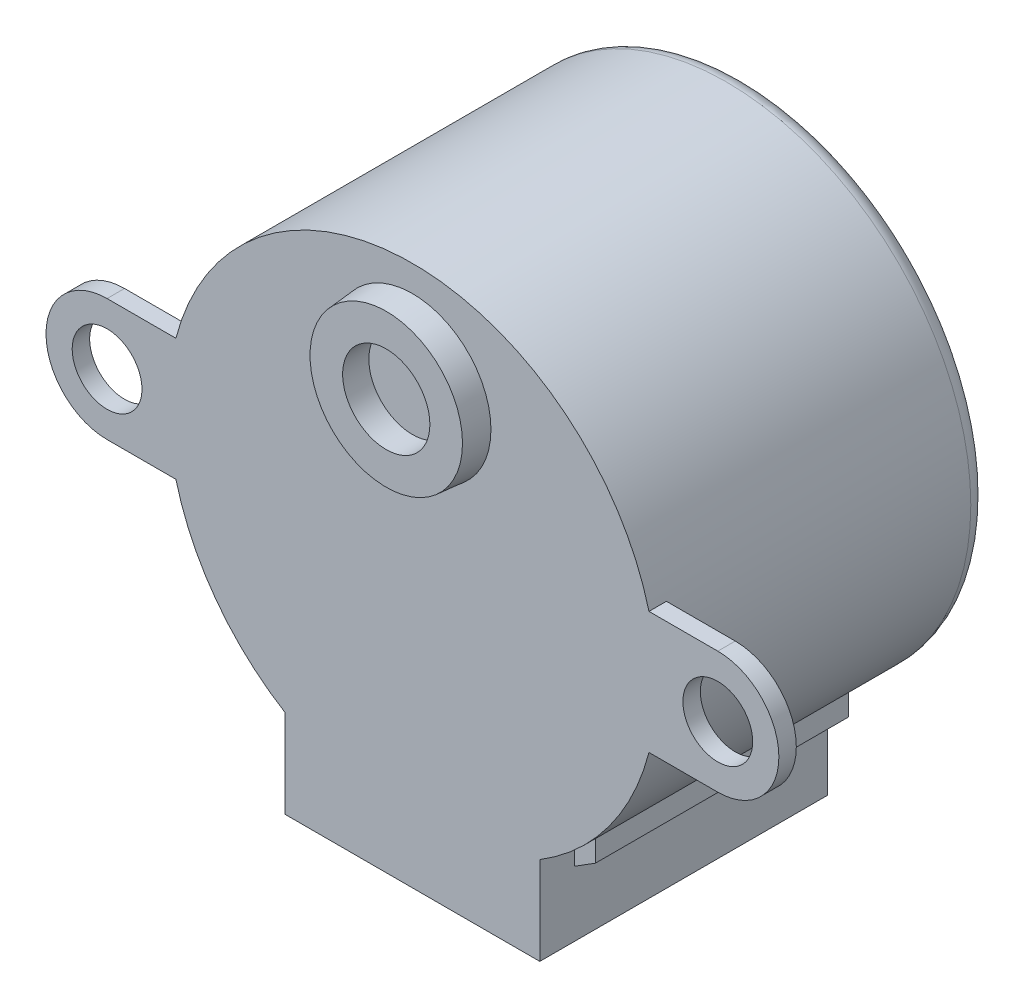
SolidWorks part; units mm, degrees
ref_plane "Front Plane" through (0, 0, 0) normal (0, 0, 1) x (1, 0, 0)
ref_plane "Top Plane" through (0, 0, 0) normal (0, 1, 0) x (1, 0, 0)
ref_plane "Right Plane" through (0, 0, 0) normal (1, 0, 0) x (0, 0, -1)
sketch "Sketch1" plane through (0, 0, 0) normal (0, 0, 1) x (1, 0, 0)
  circle A0 centre (0, 0) radius 14
  dimension "D1" = 28
extrude "Boss-Extrude3" add sketch "Sketch1" along normal blind 19
sketch "Sketch5" plane through (0, 0, 19) normal (0, 0, 1) x (1, 0, 0)
  line L0 (0, 0) -> (0, -22.9361) construction
  line L1 (-7.3, -11.9461) -> (-7.3, -17)
  line L2 (-7.3, -17) -> (7.3, -17)
  line L3 (7.3, -11.9461) -> (7.3, -17)
  circle A0 centre (0, 0) radius 14 construction
  arc A1 (7.3, -11.9461) -> (-7.3, -11.9461) centre (0, 0) cw
  point P9 (0, -17)
  dimension "D1" = 14.6
  dimension "D2" = 17
extrude "Boss-Extrude5" add sketch "Sketch5" against normal blind 16.5
sketch "Sketch6" plane through (0, 0, 2.5) normal (0, 0, -1) x (-1, 0, 0)
  line L0 (-8.4859, -11.135) -> (-8.4859, -12.5311)
  line L1 (-8.4859, -12.5311) -> (-7.3, -13.2752)
  line L2 (-7.3, -17) -> (-7.3, -11.9461) construction
  line L3 (-7.3, -13.2752) -> (-7.3, -11.9461)
  line L4 (-7.3, -11.9461) -> (-8.4859, -11.135)
  line L5 (0, 10.45) -> (0, -10.45) construction
  line L6 (7.3, -13.2752) -> (7.3, -11.9461)
  line L7 (8.4859, -12.5311) -> (7.3, -13.2752)
  line L8 (8.4859, -11.135) -> (8.4859, -12.5311)
  line L9 (7.3, -11.9461) -> (8.4859, -11.135)
  circle A0 centre (0, 0) radius 14 construction
  arc A1 (-7.3, -11.9461) -> (7.3, -11.9461) centre (0, 0) ccw construction
extrude "Boss-Extrude7" add sketch "Sketch6" against normal blind 14.5
fillet "Fillet1" radius 1 1 edges at (14, 0, 0)
sketch "Sketch7" plane through (0, 0, 19) normal (0, 0, 1) x (1, 0, 0)
  line L0 (0, 0) -> (20.6615, 0) construction
  line L1 (13.5554, 3.5) -> (17.5, 3.5)
  line L2 (17.5, -3.5) -> (13.5554, -3.5)
  circle A0 centre (17.5, 0) radius 2
  arc A1 (7.3, -11.9461) -> (-7.3, -11.9461) centre (0, 0) ccw construction
  arc A2 (17.5, 3.5) -> (17.5, -3.5) centre (17.5, 0) cw
  arc A3 (13.5554, 3.5) -> (13.5554, -3.5) centre (0, 0) cw
  dimension "D1" = 4
  dimension "D2" = 17.5
  dimension "D3" = 7
extrude "Boss-Extrude8" add sketch "Sketch7" against normal blind 1
mirror "Mirror1" about plane through (0, 0, 0) normal (1, 0, 0) of "Boss-Extrude8"
sketch "Sketch8" plane through (0, 0, 19) normal (0, 0, 1) x (1, 0, 0)
  line L0 (0, 0) -> (0, 16) construction
  circle A0 centre (0, 8) radius 4.5
  point P5 (0, 0)
  point P6 (0, 0)
  dimension "D1" = 9
  dimension "D2" = 8
extrude "Boss-Extrude9" add sketch "Sketch8" along normal blind 1.5 draft 5
sketch "Sketch9" plane through (0, 0, 20.5) normal (0, 0, 1) x (1, 0, 0)
  circle A0 centre (0, 8) radius 2.5
  dimension "D1" = 5
extrude "Cut-Extrude1" cut sketch "Sketch9" against normal up to surface (1.5 mm away) up to face at (4.5, 8, 19)
sketch "Sketch10" plane through (0, 0, 0) normal (0, 0, -1) x (-1, 0, 0)
  line L0 (-1.4331, 5.31) -> (-0.684, 8.7977)
  line L1 (-0.684, 8.7977) -> (0.684, 8.7977)
  line L2 (0, 11.275) -> (0, -11.275) construction
  line L3 (1.4331, 5.31) -> (0.684, 8.7977)
  line L4 (2.7414, 4.7681) -> (5.7373, 6.7046)
  line L5 (4.7681, 2.7414) -> (6.7046, 5.7373)
  line L6 (5.7373, 6.7046) -> (6.7046, 5.7373)
  line L7 (5.31, 1.4331) -> (8.7977, 0.684)
  line L8 (5.31, -1.4331) -> (8.7977, -0.684)
  line L9 (8.7977, 0.684) -> (8.7977, -0.684)
  line L10 (4.7681, -2.7414) -> (6.7046, -5.7373)
  line L11 (2.7414, -4.7681) -> (5.7373, -6.7046)
  line L12 (6.7046, -5.7373) -> (5.7373, -6.7046)
  line L13 (1.4331, -5.31) -> (0.684, -8.7977)
  line L14 (-1.4331, -5.31) -> (-0.684, -8.7977)
  line L15 (0.684, -8.7977) -> (-0.684, -8.7977)
  line L16 (-2.7414, -4.7681) -> (-5.7373, -6.7046)
  line L17 (-4.7681, -2.7414) -> (-6.7046, -5.7373)
  line L18 (-5.7373, -6.7046) -> (-6.7046, -5.7373)
  line L19 (-5.31, -1.4331) -> (-8.7977, -0.684)
  line L20 (-5.31, 1.4331) -> (-8.7977, 0.684)
  line L21 (-8.7977, -0.684) -> (-8.7977, 0.684)
  line L22 (-4.7681, 2.7414) -> (-6.7046, 5.7373)
  line L23 (-2.7414, 4.7681) -> (-5.7373, 6.7046)
  line L24 (-6.7046, 5.7373) -> (-5.7373, 6.7046)
  arc A0 (-2.7414, 4.7681) -> (-4.7681, 2.7414) centre (0, 0) ccw
  arc A1 (-1.4331, 5.31) -> (1.4331, 5.31) centre (0, 0) cw
  arc A2 (-2.7414, 4.7681) -> (-4.7681, 2.7414) centre (0, 0) ccw
  arc A3 (-2.7414, 4.7681) -> (-4.7681, 2.7414) centre (0, 0) ccw
  arc A4 (-2.7414, 4.7681) -> (-4.7681, 2.7414) centre (0, 0) ccw
  arc A5 (-2.7414, 4.7681) -> (-4.7681, 2.7414) centre (0, 0) ccw
  arc A6 (-2.7414, 4.7681) -> (-4.7681, 2.7414) centre (0, 0) ccw
  arc A7 (-2.7414, 4.7681) -> (-4.7681, 2.7414) centre (0, 0) ccw
  arc A8 (-2.7414, 4.7681) -> (-4.7681, 2.7414) centre (0, 0) ccw
  arc A9 (-5.31, 1.4331) -> (-5.31, -1.4331) centre (0, 0) ccw
  arc A10 (-5.31, 1.4331) -> (-5.31, -1.4331) centre (0, 0) ccw
  arc A11 (-5.31, 1.4331) -> (-5.31, -1.4331) centre (0, 0) ccw
  arc A12 (-5.31, 1.4331) -> (-5.31, -1.4331) centre (0, 0) ccw
  arc A13 (-5.31, 1.4331) -> (-5.31, -1.4331) centre (0, 0) ccw
  arc A14 (-5.31, 1.4331) -> (-5.31, -1.4331) centre (0, 0) ccw
  arc A15 (-5.31, 1.4331) -> (-5.31, -1.4331) centre (0, 0) ccw
  arc A16 (-4.7681, -2.7414) -> (-2.7414, -4.7681) centre (0, 0) ccw
  arc A17 (-4.7681, -2.7414) -> (-2.7414, -4.7681) centre (0, 0) ccw
  arc A18 (-4.7681, -2.7414) -> (-2.7414, -4.7681) centre (0, 0) ccw
  arc A19 (-4.7681, -2.7414) -> (-2.7414, -4.7681) centre (0, 0) ccw
  arc A20 (-4.7681, -2.7414) -> (-2.7414, -4.7681) centre (0, 0) ccw
  arc A21 (-4.7681, -2.7414) -> (-2.7414, -4.7681) centre (0, 0) ccw
  arc A22 (-4.7681, -2.7414) -> (-2.7414, -4.7681) centre (0, 0) ccw
  arc A23 (-4.7681, -2.7414) -> (-2.7414, -4.7681) centre (0, 0) ccw
  arc A24 (-1.4331, -5.31) -> (1.4331, -5.31) centre (0, 0) ccw
  arc A25 (-1.4331, -5.31) -> (1.4331, -5.31) centre (0, 0) ccw
  arc A26 (-1.4331, -5.31) -> (1.4331, -5.31) centre (0, 0) ccw
  arc A27 (-1.4331, -5.31) -> (1.4331, -5.31) centre (0, 0) ccw
  arc A28 (-1.4331, -5.31) -> (1.4331, -5.31) centre (0, 0) ccw
  arc A29 (-1.4331, -5.31) -> (1.4331, -5.31) centre (0, 0) ccw
  arc A30 (-1.4331, -5.31) -> (1.4331, -5.31) centre (0, 0) ccw
  arc A31 (-1.4331, -5.31) -> (1.4331, -5.31) centre (0, 0) ccw
  arc A32 (2.7414, -4.7681) -> (4.7681, -2.7414) centre (0, 0) ccw
  arc A33 (2.7414, -4.7681) -> (4.7681, -2.7414) centre (0, 0) ccw
  arc A34 (2.7414, -4.7681) -> (4.7681, -2.7414) centre (0, 0) ccw
  arc A35 (2.7414, -4.7681) -> (4.7681, -2.7414) centre (0, 0) ccw
  arc A36 (2.7414, -4.7681) -> (4.7681, -2.7414) centre (0, 0) ccw
  arc A37 (2.7414, -4.7681) -> (4.7681, -2.7414) centre (0, 0) ccw
  arc A38 (2.7414, -4.7681) -> (4.7681, -2.7414) centre (0, 0) ccw
  arc A39 (2.7414, -4.7681) -> (4.7681, -2.7414) centre (0, 0) ccw
  arc A40 (5.31, -1.4331) -> (5.31, 1.4331) centre (0, 0) ccw
  arc A41 (5.31, -1.4331) -> (5.31, 1.4331) centre (0, 0) ccw
  arc A42 (5.31, -1.4331) -> (5.31, 1.4331) centre (0, 0) ccw
  arc A43 (5.31, -1.4331) -> (5.31, 1.4331) centre (0, 0) ccw
  arc A44 (5.31, -1.4331) -> (5.31, 1.4331) centre (0, 0) ccw
  arc A45 (5.31, -1.4331) -> (5.31, 1.4331) centre (0, 0) ccw
  arc A46 (5.31, -1.4331) -> (5.31, 1.4331) centre (0, 0) ccw
  arc A47 (5.31, -1.4331) -> (5.31, 1.4331) centre (0, 0) ccw
  arc A48 (4.7681, 2.7414) -> (2.7414, 4.7681) centre (0, 0) ccw
  arc A49 (4.7681, 2.7414) -> (2.7414, 4.7681) centre (0, 0) ccw
  arc A50 (4.7681, 2.7414) -> (2.7414, 4.7681) centre (0, 0) ccw
  arc A51 (4.7681, 2.7414) -> (2.7414, 4.7681) centre (0, 0) ccw
  arc A52 (4.7681, 2.7414) -> (2.7414, 4.7681) centre (0, 0) ccw
  arc A53 (4.7681, 2.7414) -> (2.7414, 4.7681) centre (0, 0) ccw
  arc A54 (4.7681, 2.7414) -> (2.7414, 4.7681) centre (0, 0) ccw
  arc A55 (4.7681, 2.7414) -> (2.7414, 4.7681) centre (0, 0) ccw
  arc A56 (1.4331, 5.31) -> (-1.4331, 5.31) centre (0, 0) ccw
  arc A57 (1.4331, 5.31) -> (-1.4331, 5.31) centre (0, 0) ccw
  arc A58 (1.4331, 5.31) -> (-1.4331, 5.31) centre (0, 0) ccw
  arc A59 (1.4331, 5.31) -> (-1.4331, 5.31) centre (0, 0) ccw
  arc A60 (1.4331, 5.31) -> (-1.4331, 5.31) centre (0, 0) ccw
  arc A61 (1.4331, 5.31) -> (-1.4331, 5.31) centre (0, 0) ccw
  arc A62 (1.4331, 5.31) -> (-1.4331, 5.31) centre (0, 0) ccw
  arc A63 (1.4331, 5.31) -> (-1.4331, 5.31) centre (0, 0) ccw
  arc A64 (-5.31, 1.4331) -> (-5.31, -1.4331) centre (0, 0) ccw
  point P1 (1.5569, 5.275)
  point P9 (0, 8.7977)
  point P10 (1.4794, 5.275)
  point P11 (0.684, 8.7977)
  point P49 (0, 0)
  dimension "D1" = 11
  dimension "D2" = 8
extrude "Cut-Extrude2" cut sketch "Sketch10" against normal blind 0.3 contours L0 A1 L3 L1 | A48 L5 L6 L4 | A40 L8 L9 L7 | A32 L11 L12 L10 | A24 L14 L15 L13 | A16 L17 L18 L16 | A9 L20 L21 L19 | A0 L23 L24 L22 region at (0, 6.924, 0) region at (-4.896, 4.896, 0) region at (-6.924, 0, 0) region at (-4.896, -4.896, 0) region at (0, -6.924, 0) region at (4.896, -4.896, 0) region at (6.924, 0, 0) region at (4.896, 4.896, 0)
